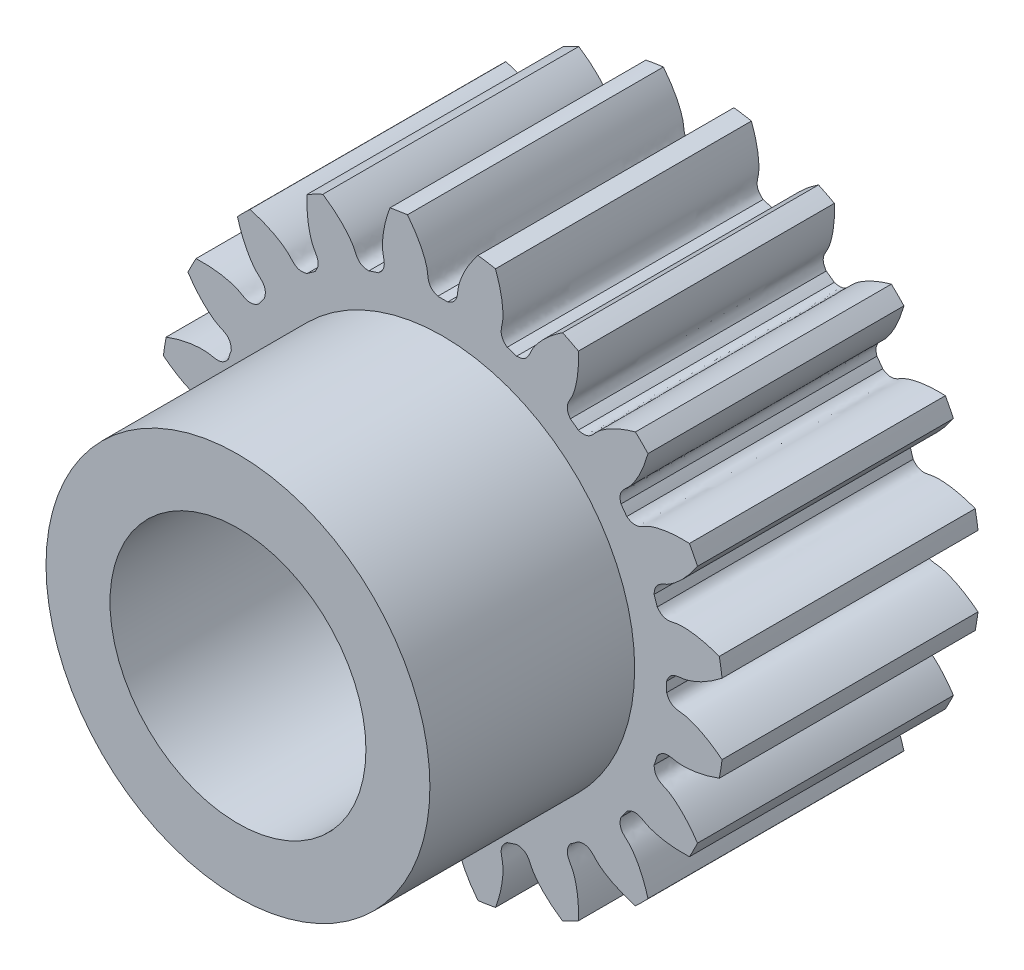
SolidWorks part; units mm, degrees
material "合金钢 (SS)"
ref_plane "前视基准面" through (0, 0, 0) normal (0, 0, 1) x (1, 0, 0)
ref_plane "上视基准面" through (0, 0, 0) normal (0, 1, 0) x (1, 0, 0)
ref_plane "右视基准面" through (0, 0, 0) normal (1, 0, 0) x (0, 0, -1)
other "Configuration Table"
sketch "草图1" plane through (0, 0, 0) normal (0, 0, 1) x (1, 0, 0)
  circle A0 centre (0, 0) radius 11
extrude "凸台-拉伸1" add sketch "草图1" along normal blind 10
ref_axis "基准轴1" through (0, 0, -1.5) along (0, 0, 1)
sketch "草图2" plane through (0, 0, 0) normal (0, 0, 1) x (1, 0, 0)
  line L0 (0, 0) -> (0, 11) construction
  circle A0 centre (0, 0) radius 11 construction
  arc A1 (0.1933, 8.7479) -> (-0.1933, 8.7479) centre (0, 0) ccw
  arc A2 (3.1812, 12.4983) -> (-3.1812, 12.4983) centre (0, 0) ccw
  spline S0 degree 3 poles (0.1933, 8.7479) (0.6112, 8.8935) (0.5571, 9.1871) (0.6129, 9.47) (0.6189, 9.4976) (0.6263, 9.5286) (0.6353, 9.5632) (0.646, 9.6012) (0.6585, 9.6426) (0.673, 9.6873) (0.6897, 9.7352) (0.7086, 9.7863) (0.7299, 9.8406) (0.7537, 9.8978) (0.7801, 9.958) (0.8094, 10.0211) (0.8415, 10.087) (0.8767, 10.1556) (0.915, 10.2267) (0.9566, 10.3004) (1.0015, 10.3764) (1.05, 10.4548) (1.102, 10.5352) (1.1578, 10.6178) (1.2173, 10.7023) (1.2808, 10.7886) (1.3482, 10.8766) (1.4198, 10.9662) (1.4955, 11.0572) (1.5755, 11.1496) (1.6598, 11.2431) (1.7486, 11.3376) (1.8418, 11.4331) (1.9397, 11.5293) (2.0421, 11.6261) (2.1493, 11.7233) (2.2612, 11.8209) (2.378, 11.9186) (2.4996, 12.0163) (2.6261, 12.1139) (2.7575, 12.2112) (2.9415, 12.3416) (3.0839, 12.4363) (3.1812, 12.4983) knots 0 0 0 0 0.165916 0.170906 0.176664 0.183189 0.190482 0.198542 0.207371 0.216967 0.22733 0.238462 0.250361 0.263027 0.276462 0.290664 0.305634 0.321371 0.337876 0.355149 0.37319 0.391998 0.411574 0.431917 0.453028 0.474907 0.497554 0.520968 0.54515 0.570099 0.595817 0.622302 0.649554 0.677575 0.706363 0.735918 0.766242 0.797333 0.829191 0.861818 0.895212 0.929373 1 1 1 1
  spline S1 degree 3 poles (-0.1933, 8.7479) (-0.6112, 8.8935) (-0.5571, 9.1871) (-0.6129, 9.47) (-0.6189, 9.4976) (-0.6263, 9.5286) (-0.6353, 9.5632) (-0.646, 9.6012) (-0.6585, 9.6426) (-0.673, 9.6873) (-0.6897, 9.7352) (-0.7086, 9.7863) (-0.7299, 9.8406) (-0.7537, 9.8978) (-0.7801, 9.958) (-0.8094, 10.0211) (-0.8415, 10.087) (-0.8767, 10.1556) (-0.915, 10.2267) (-0.9566, 10.3004) (-1.0015, 10.3764) (-1.05, 10.4548) (-1.102, 10.5352) (-1.1578, 10.6178) (-1.2173, 10.7023) (-1.2808, 10.7886) (-1.3482, 10.8766) (-1.4198, 10.9662) (-1.4955, 11.0572) (-1.5755, 11.1496) (-1.6598, 11.2431) (-1.7486, 11.3376) (-1.8418, 11.4331) (-1.9397, 11.5293) (-2.0421, 11.6261) (-2.1493, 11.7233) (-2.2612, 11.8209) (-2.378, 11.9186) (-2.4996, 12.0163) (-2.6261, 12.1139) (-2.7575, 12.2112) (-2.9415, 12.3416) (-3.0839, 12.4363) (-3.1812, 12.4983) knots 0 0 0 0 0.165916 0.170906 0.176664 0.183189 0.190482 0.198542 0.207371 0.216967 0.22733 0.238462 0.250361 0.263027 0.276462 0.290664 0.305634 0.321371 0.337876 0.355149 0.37319 0.391998 0.411574 0.431917 0.453028 0.474907 0.497554 0.520968 0.54515 0.570099 0.595817 0.622302 0.649554 0.677575 0.706363 0.735918 0.766242 0.797333 0.829191 0.861818 0.895212 0.929373 1 1 1 1
extrude "切除-拉伸1" cut sketch "草图2" along normal through all
pattern_circular "阵列(圆周)1" count 20 every 18 about axis through (0, 0, -1.5) along (0, 0, 1) of "切除-拉伸1"
sketch "草图3" plane through (0, 0, 0) normal (0, 0, 1) x (1, 0, 0)
  circle A0 centre (0, 0) radius 10 construction
  dimension "Dn" = 20
sketch "草图4" plane through (0, 0, 10) normal (0, 0, 1) x (1, 0, 0)
  circle A0 centre (0, 0) radius 7.5
  dimension "D1" = 15
extrude "凸台-拉伸2" add sketch "草图4" along normal blind 8
sketch "草图5" plane through (0, 0, 18) normal (0, 0, 1) x (1, 0, 0)
  circle A0 centre (0, 0) radius 5
  dimension "D1" = 10
extrude "切除-拉伸2" cut sketch "草图5" against normal blind 38
